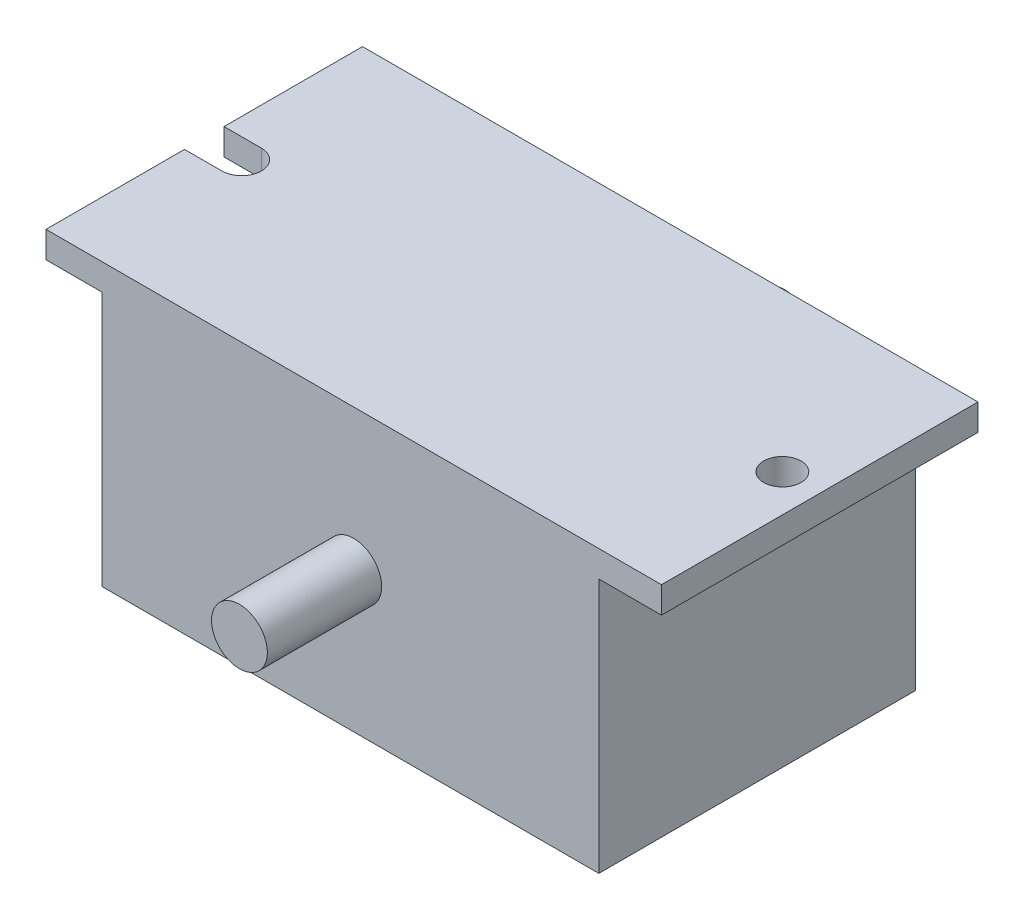
SolidWorks part; units mm, degrees
ref_plane "Front Plane" through (0, 0, 0) normal (0, 0, 1) x (1, 0, 0)
ref_plane "Top Plane" through (0, 0, 0) normal (0, 1, 0) x (1, 0, 0)
ref_plane "Right Plane" through (0, 0, 0) normal (1, 0, 0) x (0, 0, -1)
sketch "Sketch1" plane through (0, 0, 0) normal (0, 0, 1) x (1, 0, 0)
  line L1 (-56.49, 32.211) -> (58.01, 32.211)
  line L2 (-57.25, 26.211) -> (-57.25, -31.789)
  line L3 (-57.25, -31.789) -> (55.75, -31.789)
  line L4 (55.75, 26.211) -> (55.75, -31.789)
  line L5 (-56.49, 32.211) -> (55.75, -31.789) construction
  line L6 (-57.25, -31.789) -> (58.01, 32.211) construction
  line L7 (70, 32.211) -> (70, 26.211)
  line L8 (70, 26.211) -> (55.75, 26.211)
  line L9 (-56.49, 32.211) -> (-70, 32.211)
  line L10 (-70, 32.211) -> (-70, 26.211)
  line L11 (-70, 26.211) -> (-57.25, 26.211)
  line L12 (58.01, 32.211) -> (70, 32.211)
  point P0 (0, 0)
  dimension "D1" = 113
  dimension "D2" = 64
  dimension "D3" = 70
  dimension "D4" = 70
  dimension "D5" = 6
  dimension "D6" = 6
  dimension "D7" = 12.75
  dimension "D8" = 114.5
extrude "Boss-Extrude1" add sketch "Sketch1" along normal blind 72
sketch "Sketch2" plane through (0, 32.211, 0) normal (0, 1, 0) x (1, 0, 0)
  line L0 (-61.5, -31.5) -> (-70, -31.5)
  line L1 (-70, -72) -> (-70, 0) construction
  line L2 (-61.5, -40.5) -> (-70, -40.5)
  line L3 (-70, -31.5) -> (-70, -40.5)
  circle A0 centre (61.5, -36) radius 4.25
  arc A1 (-61.5, -40.5) -> (-61.5, -31.5) centre (-61.5, -36) ccw
  dimension "D3" = 8.5
  dimension "D6" = 9
  dimension "D1" = 61.5
  dimension "D2" = 36
  dimension "D4" = 36
  dimension "D5" = 61.5
extrude "Cut-Extrude1" cut sketch "Sketch2" against normal through all
sketch "Sketch3" plane through (0, 0, 72) normal (0, 0, 1) x (1, 0, 0)
  circle A0 centre (0, 0) radius 6.35
  dimension "D1" = 12.7
extrude "Boss-Extrude2" add sketch "Sketch3" along normal blind 26
sketch "Sketch5" plane through (0, 0, 0) normal (0, 0, -1) x (-1, 0, 0)
  circle A0 centre (0, 0) radius 6.35
  dimension "D1" = 12.7
extrude "Boss-Extrude3" add sketch "Sketch5" along normal blind 26
